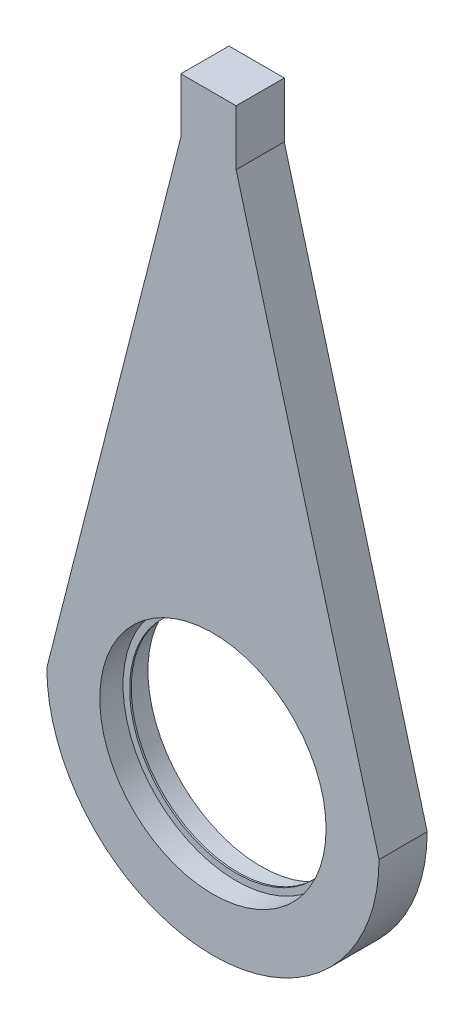
SolidWorks part; units mm, degrees
ref_plane "Front Plane" through (0, 0, 0) normal (0, 0, 1) x (1, 0, 0)
ref_plane "Top Plane" through (0, 0, 0) normal (0, 1, 0) x (1, 0, 0)
ref_plane "Right Plane" through (0, 0, 0) normal (1, 0, 0) x (0, 0, -1)
sketch "Sketch1" plane through (0, 0, 0) normal (0, 0, 1) x (1, 0, 0)
  line L1 (4.8191, 120.75) -> (-6.6809, 120.75)
  line L2 (4.8191, 120.75) -> (4.8191, 109.25)
  line L4 (-6.6809, 120.75) -> (-6.6809, 109.25)
  line L5 (-34.5, 0) -> (-6.6809, 109.25)
  line L6 (4.8191, 109.25) -> (34.5, 0)
  arc A1 (-34.5, 0) -> (34.5, 0) centre (0, 0) ccw
  point P0 (-0.9309, 115)
  dimension "D1" = 11.5
  dimension "D2" = 11.5
  dimension "D3" = 115
extrude "Boss-Extrude1" add sketch "Sketch1" along normal mid plane 10
sketch "Sketch2" plane through (0, 0, 0) normal (0, 0, 1) x (1, 0, 0)
  circle A0 centre (0, 0) radius 23.5
  dimension "D1" = 47
extrude "Cut-Extrude1" cut sketch "Sketch2" against normal blind 4.83 from surface starting at face at (-0.6206, 70.9167, 5)
extrude "Cut-Extrude2" cut sketch "Sketch2<2>" along normal blind 4.83 from surface starting at face at (-0.6206, 70.9167, -5)
sketch "Sketch2<2>" plane through (0, 0, 0) normal (0, 0, 1) x (1, 0, 0) same geometry as "Sketch2"
sketch "Sketch3" plane through (0, 0, 0) normal (0, 0, 1) x (1, 0, 0)
  circle A0 centre (0, 0) radius 22.1375
  dimension "D1" = 44.275
extrude "Cut-Extrude3" cut sketch "Sketch3" against normal through all both and the other way through all
